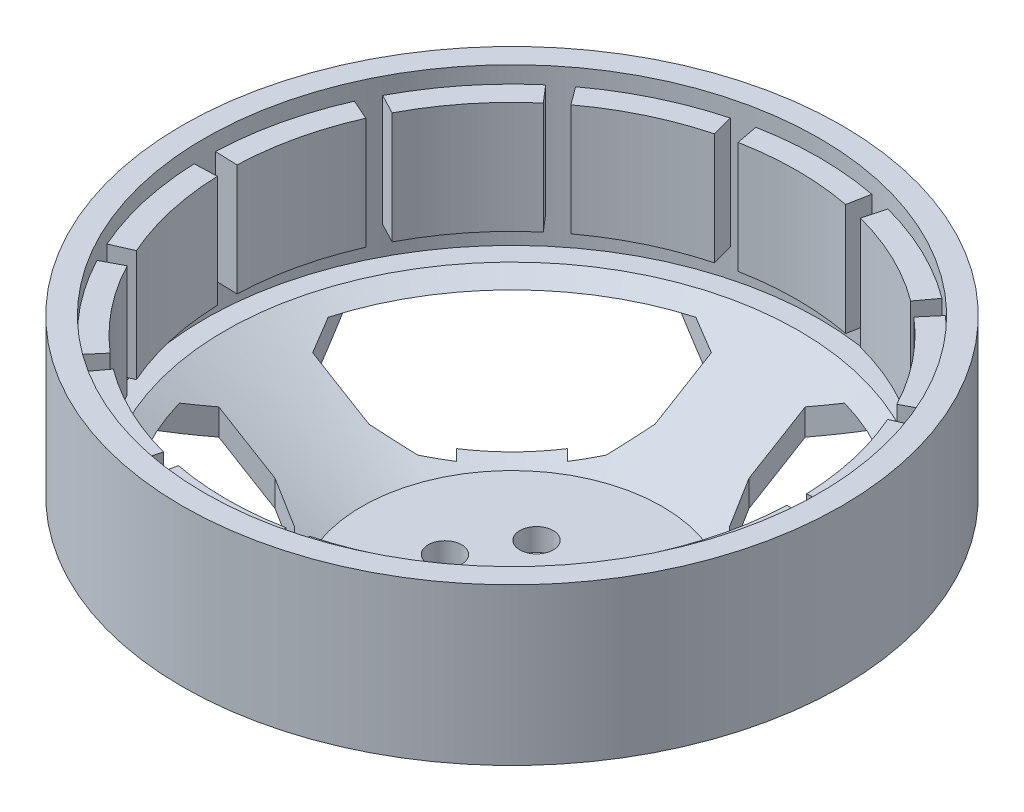
SolidWorks part; units mm, degrees
material "Stainless Steel (ferritic)"
ref_plane "Ön Düzlem" through (0, 0, 0) normal (0, 0, 1) x (1, 0, 0)
ref_plane "Üst Düzlem" through (0, 0, 0) normal (0, 1, 0) x (1, 0, 0)
ref_plane "Sağ Düzlem" through (0, 0, 0) normal (1, 0, 0) x (0, 0, -1)
sketch "Çizim1" plane through (0, 0, 0) normal (0, 1, 0) x (1, 0, 0)
  circle A0 centre (0, 0) radius 29.5
  circle A1 centre (0, 0) radius 27.5
  dimension "D1" = 59
  dimension "D2" = 2
extrude "Yükseklik-Ekstrüzyon1" add sketch "Çizim1" along normal blind 12
sketch "Çizim2" plane through (0, 0, 0) normal (0, 1, 0) x (1, 0, 0)
  line L0 (6.5305, 24.6496) -> (7.0427, 26.5829)
  line L1 (-4.8113, 25.042) -> (-5.1887, 27.0061)
  line L2 (4.8113, 25.042) -> (5.1887, 27.0061)
  line L3 (15.2002, 20.4745) -> (16.3923, 22.0803)
  line L4 (16.5788, 19.3751) -> (17.8791, 20.8947)
  line L5 (22.5784, 11.8518) -> (24.3493, 12.7813)
  line L6 (23.3435, 10.2631) -> (25.1744, 11.068)
  line L7 (25.4848, 0.8817) -> (27.4836, 0.9508)
  line L8 (25.4848, -0.8817) -> (27.4836, -0.9508)
  line L9 (23.3435, -10.2631) -> (25.1744, -11.068)
  line L10 (22.5784, -11.8518) -> (24.3493, -12.7813)
  line L11 (16.5788, -19.3751) -> (17.8791, -20.8947)
  line L12 (15.2002, -20.4745) -> (16.3923, -22.0803)
  line L13 (6.5305, -24.6496) -> (7.0427, -26.5829)
  line L14 (4.8113, -25.042) -> (5.1887, -27.0061)
  line L15 (-4.8113, -25.042) -> (-5.1887, -27.0061)
  line L16 (-6.5305, -24.6496) -> (-7.0427, -26.5829)
  line L17 (-15.2002, -20.4745) -> (-16.3923, -22.0803)
  line L18 (-16.5788, -19.3751) -> (-17.8791, -20.8947)
  line L19 (-22.5784, -11.8518) -> (-24.3493, -12.7813)
  line L20 (-23.3435, -10.2631) -> (-25.1744, -11.068)
  line L21 (-25.4848, -0.8817) -> (-27.4836, -0.9508)
  line L22 (-25.4848, 0.8817) -> (-27.4836, 0.9508)
  line L23 (-23.3435, 10.2631) -> (-25.1744, 11.068)
  line L24 (-22.5784, 11.8518) -> (-24.3493, 12.7813)
  line L25 (-16.5788, 19.3751) -> (-17.8791, 20.8947)
  line L26 (-15.2002, 20.4745) -> (-16.3923, 22.0803)
  line L27 (-6.5305, 24.6496) -> (-7.0427, 26.5829)
  arc A0 (4.8113, 25.042) -> (-4.8113, 25.042) centre (0, 0) ccw
  circle A2 centre (0, 0) radius 27.5 construction
  arc A3 (15.2002, 20.4745) -> (6.5305, 24.6496) centre (0, 0) ccw
  arc A4 (22.5784, 11.8518) -> (16.5788, 19.3751) centre (0, 0) ccw
  arc A5 (25.4848, 0.8817) -> (23.3435, 10.2631) centre (0, 0) ccw
  arc A6 (23.3435, -10.2631) -> (25.4848, -0.8817) centre (0, 0) ccw
  arc A7 (16.5788, -19.3751) -> (22.5784, -11.8518) centre (0, 0) ccw
  arc A8 (6.5305, -24.6496) -> (15.2002, -20.4745) centre (0, 0) ccw
  arc A9 (-4.8113, -25.042) -> (4.8113, -25.042) centre (0, 0) ccw
  arc A10 (-15.2002, -20.4745) -> (-6.5305, -24.6496) centre (0, 0) ccw
  arc A11 (-22.5784, -11.8518) -> (-16.5788, -19.3751) centre (0, 0) ccw
  arc A12 (-25.4848, -0.8817) -> (-23.3435, -10.2631) centre (0, 0) ccw
  arc A13 (-23.3435, 10.2631) -> (-25.4848, 0.8817) centre (0, 0) ccw
  arc A14 (-16.5788, 19.3751) -> (-22.5784, 11.8518) centre (0, 0) ccw
  arc A15 (-6.5305, 24.6496) -> (-15.2002, 20.4745) centre (0, 0) ccw
  arc A16 (-25.1744, 11.068) -> (-27.4836, 0.9508) centre (0, 0) ccw
  arc A17 (-7.0427, 26.5829) -> (-16.3923, 22.0803) centre (0, 0) ccw
  arc A18 (-7.0427, 26.5829) -> (-16.3923, 22.0803) centre (0, 0) ccw
  arc A19 (-17.8791, 20.8947) -> (-24.3493, 12.7813) centre (0, 0) ccw
  arc A20 (-17.8791, 20.8947) -> (-24.3493, 12.7813) centre (0, 0) ccw
  arc A21 (-25.1744, 11.068) -> (-27.4836, 0.9508) centre (0, 0) ccw
  arc A22 (-27.4836, -0.9508) -> (-25.1744, -11.068) centre (0, 0) ccw
  arc A23 (-27.4836, -0.9508) -> (-25.1744, -11.068) centre (0, 0) ccw
  arc A24 (-24.3493, -12.7813) -> (-17.8791, -20.8947) centre (0, 0) ccw
  arc A25 (-24.3493, -12.7813) -> (-17.8791, -20.8947) centre (0, 0) ccw
  arc A26 (-16.3923, -22.0803) -> (-7.0427, -26.5829) centre (0, 0) ccw
  arc A27 (-16.3923, -22.0803) -> (-7.0427, -26.5829) centre (0, 0) ccw
  arc A28 (-5.1887, -27.0061) -> (5.1887, -27.0061) centre (0, 0) ccw
  arc A29 (-5.1887, -27.0061) -> (5.1887, -27.0061) centre (0, 0) ccw
  arc A30 (7.0427, -26.5829) -> (16.3923, -22.0803) centre (0, 0) ccw
  arc A31 (7.0427, -26.5829) -> (16.3923, -22.0803) centre (0, 0) ccw
  arc A32 (17.8791, -20.8947) -> (24.3493, -12.7813) centre (0, 0) ccw
  arc A33 (17.8791, -20.8947) -> (24.3493, -12.7813) centre (0, 0) ccw
  arc A34 (25.1744, -11.068) -> (27.4836, -0.9508) centre (0, 0) ccw
  arc A35 (25.1744, -11.068) -> (27.4836, -0.9508) centre (0, 0) ccw
  arc A36 (27.4836, 0.9508) -> (25.1744, 11.068) centre (0, 0) ccw
  arc A37 (27.4836, 0.9508) -> (25.1744, 11.068) centre (0, 0) ccw
  arc A38 (24.3493, 12.7813) -> (17.8791, 20.8947) centre (0, 0) ccw
  arc A39 (24.3493, 12.7813) -> (17.8791, 20.8947) centre (0, 0) ccw
  arc A40 (16.3923, 22.0803) -> (7.0427, 26.5829) centre (0, 0) ccw
  arc A41 (16.3923, 22.0803) -> (7.0427, 26.5829) centre (0, 0) ccw
  arc A42 (5.1887, 27.0061) -> (-5.1887, 27.0061) centre (0, 0) ccw
  arc A43 (5.1887, 27.0061) -> (-5.1887, 27.0061) centre (0, 0) ccw
  point P65 (0, 0)
  dimension "D1" = 2
  dimension "D2" = 14
extrude "Yükseklik-Ekstrüzyon3" add sketch "Çizim2" along normal blind 10 from offset 0.5 contours L2 A42 L1 A0 | L27 A17 L26 A15 | L25 A19 L24 A14 | L23 A16 L22 A13 | L21 A22 L20 A12 | L19 A24 L18 A11 | L17 A26 L16 A10 | L15 A28 L14 A9 | L13 A30 L12 A8 | L11 A32 L10 A7 | L9 A34 L8 A6 | L7 A36 L6 A5 | L5 A38 L4 A4 | L3 A40 L0 A3 region at (11.4344, 0, -23.7438) region at (0, 0, -26.3537) region at (20.6041, 0, -16.4312) region at (25.6929, 0, -5.8642) region at (25.6929, 0, 5.8642) region at (20.6041, 0, 16.4312) region at (11.4344, 0, 23.7438) region at (0, 0, 26.3537) region at (-11.4344, 0, 23.7438) region at (-20.6041, 0, 16.4312) region at (-25.6929, 0, 5.8642) region at (-25.6929, 0, -5.8642) region at (-20.6041, 0, -16.4312) region at (-11.4344, 0, -23.7438)
sketch "Çizim3" plane through (0, 0, 0) normal (0, -1, 0) x (1, 0, 0)
  circle A0 centre (0, 0) radius 29.5
  circle A1 centre (0, 0) radius 27.5
extrude "Yükseklik-Ekstrüzyon4" add sketch "Çizim3" along normal blind 2
sketch3d "3B Çizim3"
  line L0 (0, -2, 0) -> (29.5, -2, 0)
  line L1 (0, -2, 0) -> (0, -11.5, 0)
  line L2 (0, -11.5, 0) -> (14, -11.5, 0)
  line L3 (14, -11.5, 0) -> (29.5, -2, 0)
  line L4 (0, 12, 0) -> (0, -2, 0) construction
  circle A1 centre (0, -2, 0) radius 29.5 construction
  point P7 (0, -31.5, 0)
  dimension "D1" = 9.5
  dimension "D2" = 14
ref_plane "Düzlem1" through (0, 0, 0) normal (0, 0, -1) x (-1, 0, 0)
sketch "Çizim6" plane through (0, 0, 0) normal (0, 0, -1) x (-1, 0, 0)
  line L0 (-29.5, -2) -> (0, -2)
  line L1 (0, -2) -> (0, -11.5)
  line L2 (0, -11.5) -> (-14, -11.5)
  line L3 (-14, -11.5) -> (-29.5, -2)
  line L4 (0, -2) -> (0, -43.9758) construction
  line L5 (0, -9.5) -> (-13.4359, -9.5)
  line L6 (-13.4359, -9.5) -> (-25.6727, -2)
  line L7 (-29.5, -2) -> (-25.6727, -2)
  line L8 (-13.4359, -9.5) -> (-28.4549, -0.2948) construction
  dimension "D1" = 2
revolve "Döndür1" add sketch "Çizim6" angle 360 about L4 region at (27.5864, -2.3099, 0)
sketch "Sketch2" plane through (0, -11.5, 0) normal (0, -1, 0) x (1, 0, 0)
  line L0 (0, 29.5) -> (0, -29.5) construction
  line L1 (-29.5, 0) -> (29.5, 0) construction
  line L2 (0, 24.75) -> (10, 27.7534)
  line L3 (0, 24.75) -> (0, 29.5)
  line L4 (4.2, 22.0371) -> (4.2, 17)
  line L5 (4.2, 22.0371) -> (13.6626, 26.1454)
  line L6 (4.2, 17) -> (5.5265, 13.9448)
  line L7 (0, 0) -> (20.8597, 20.8597) construction
  line L8 (17, 4.2) -> (13.9448, 5.5265)
  line L9 (22.0371, 4.2) -> (26.1454, 13.6626)
  line L10 (22.0371, 4.2) -> (17, 4.2)
  line L11 (24.75, 0) -> (29.5, 0)
  line L12 (24.75, 0) -> (27.7534, 10)
  line L13 (5.5265, 13.9448) -> (7.2608, 12.2105)
  line L14 (7.2608, 12.2105) -> (7.798, 12.7478)
  line L15 (7.798, 12.7478) -> (12.7478, 7.798)
  line L16 (13.9448, 5.5265) -> (12.2105, 7.2608)
  line L17 (12.2105, 7.2608) -> (12.7478, 7.798)
  circle A0 centre (0, 0) radius 29.5 construction
  arc A1 (0, 29.5) -> (10, 27.7534) centre (0, 0) cw
  circle A2 centre (0, 0) radius 14 construction
  arc A3 (29.5, 0) -> (27.7534, 10) centre (0, 0) ccw
  arc A4 (13.6626, 26.1454) -> (26.1454, 13.6626) centre (0, 0) cw
  point P29 (10.2729, 10.2729)
  dimension "D7" = 1
  dimension "D1" = 4.75
  dimension "D2" = 10
  dimension "D3" = 4.2
  dimension "D4" = 5
  dimension "D5" = 3
  dimension "D6" = 4
  dimension "D8" = 45
  dimension "D9" = 3.5
extrude "Cut-Extrude2" cut sketch "Sketch2" against normal blind 8.5
pattern_circular "CirPattern1" count 4 over 360 about axis through (0, -2, 0) along (0, -1, 0) of "Cut-Extrude2"
sketch "Çizim10" plane through (0, -11.5, 0) normal (0, -1, 0) x (1, 0, 0)
  line L0 (2, 0) -> (14, 0) construction
  line L1 (0, 0) -> (0, 11.7171) construction
  circle A0 centre (0, 0) radius 2
  circle A1 centre (0, 0) radius 14 construction
  circle A2 centre (6, 0) radius 1.5
  circle A3 centre (-6, 0) radius 1.5
  circle A4 centre (-3, 5.1962) radius 1.5
  circle A5 centre (3, 5.1962) radius 1.5
  circle A6 centre (6, 0) radius 1.5
  circle A7 centre (3, -5.1962) radius 1.5
  circle A8 centre (-3, -5.1962) radius 1.5
  point P25 (0, 0)
  dimension "D1" = 4
  dimension "D3" = 3
  dimension "D2" = 6
  dimension "D4" = 6
extrude "Kes-Ekstrüzyon2" cut sketch "Çizim10" against normal up to next and the other way through all contours A3 | A4 | A5 | A2 | A7 | A8 | A0
